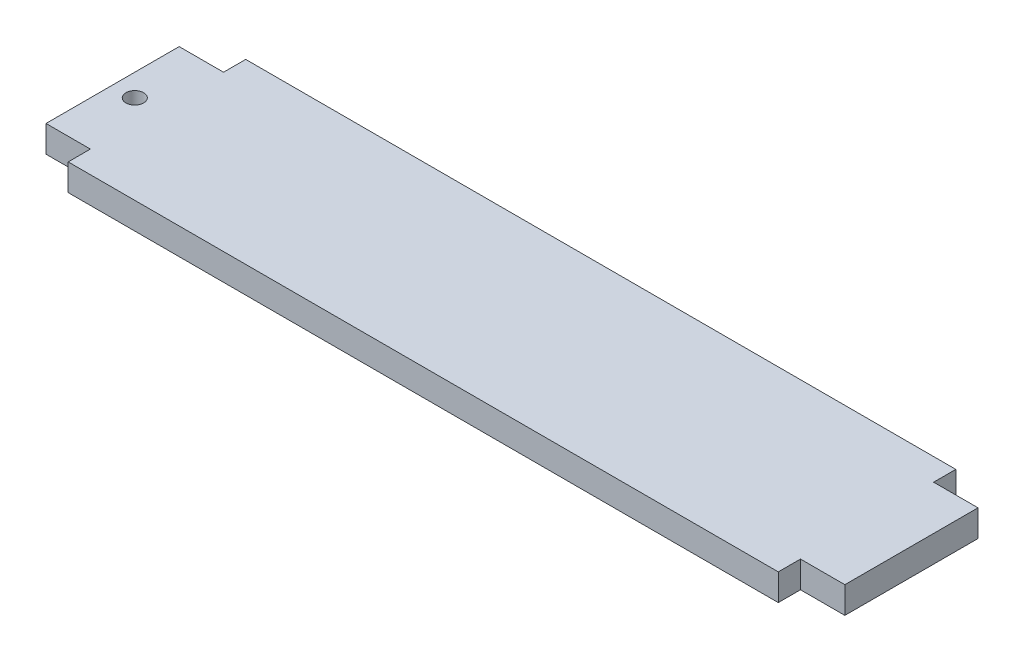
SolidWorks part; units mm, degrees
ref_plane "Front Plane" through (0, 0, 0) normal (0, 0, 1) x (1, 0, 0)
ref_plane "Top Plane" through (0, 0, 0) normal (0, 1, 0) x (1, 0, 0)
ref_plane "Right Plane" through (0, 0, 0) normal (1, 0, 0) x (0, 0, -1)
sketch "Sketch1" plane through (0, 0, 0) normal (1, 0, 0) x (0, 0, -1)
  line L1 (-10.1369, 5.602) -> (9.8631, 5.602)
  line L2 (-10.1369, 5.602) -> (-10.1369, 2.602)
  line L3 (-10.1369, 2.602) -> (9.8631, 2.602)
  line L4 (9.8631, 5.602) -> (9.8631, 2.602)
  dimension "D1" = 20
  dimension "D2" = 3
extrude "Boss-Extrude1" add sketch "Sketch1" along normal blind 90
sketch "Sketch2" plane through (0, 2.602, 0) normal (0, -1, 0) x (1, 0, 0)
  line L1 (0, -9.8631) -> (5, -9.8631)
  line L2 (0, -9.8631) -> (0, -7.3631)
  line L3 (0, -7.3631) -> (5, -7.3631)
  line L4 (5, -9.8631) -> (5, -7.3631)
  dimension "D1" = 5
  dimension "D2" = 2.5
extrude "Cut-Extrude1" cut sketch "Sketch2" against normal blind 90
sketch "Sketch5" plane through (0, 0, 0) normal (-1, 0, 0) x (0, 0, 1)
  line L0 (0, 2.602) -> (0, 5.602) construction
  line L1 (10.1369, 2.602) -> (-7.3631, 2.602) construction
  line L2 (-7.3631, 5.602) -> (10.1369, 5.602) construction
sketch "Sketch6" plane through (0, 5.602, 0) normal (0, 1, 0) x (1, 0, 0)
  line L1 (0, -10.1369) -> (5, -10.1369)
  line L2 (0, -10.1369) -> (0, -7.6369)
  line L3 (0, -7.6369) -> (5, -7.6369)
  line L4 (5, -10.1369) -> (5, -7.6369)
  dimension "D1" = 5
  dimension "D2" = 2.5
extrude "Cut-Extrude2" cut sketch "Sketch6" against normal blind 90 contours L3 L4 L1 L2
sketch "Sketch7" plane through (0, 5.602, 0) normal (0, 1, 0) x (1, 0, 0)
  line L0 (90, -0.1369) -> (0, 0) construction
  line L1 (90, 9.8631) -> (90, -10.1369) construction
  line L2 (45, -0.0684) -> (45, -10.1369) construction
  line L3 (90, -10.1369) -> (5, -10.1369) construction
sketch "Sketch8" plane through (0, 0, 10.1369) normal (0, 0, 1) x (1, 0, 0)
  line L0 (45, 5.602) -> (45, 2.602) construction
  line L1 (90, 2.602) -> (5, 2.602) construction
ref_plane "Plane3" through (45, 0, 0) normal (1, 0, 0) x (0, 0, -1)
mirror "Mirror2" about plane through (45, 0, 0) normal (1, 0, 0) of "Cut-Extrude1", "Cut-Extrude2"
sketch "Sketch9" plane through (0, 2.602, 0) normal (0, -1, 0) x (-1, 0, 0)
  line L0 (-2.5, 7.3631) -> (-2.5, -7.6369) construction
  line L1 (-5, 7.3631) -> (0, 7.3631) construction
  line L2 (0, -7.6369) -> (-5, -7.6369) construction
  line L3 (-2.5, -0.1369) -> (0, -0.1369) construction
  line L4 (0, -7.6369) -> (0, 7.3631) construction
hole_wizard "Ø2.0mm Dowel Hole1" positions "3DSketch1" profile "Sketch11" hole size "Ø2.0" standard "ISO"
sketch3d "3DSketch1"
  point P0 (2.5, 2.602, 0.1369)
sketch "Sketch11" plane through (2.5, 2.602, 0.1369) normal (1, 0, 0) x (0, 0, -1)
  line L0 (0, 0) -> (0, 13.3509)
  line L1 (0, 13.3509) -> (1, 12.75)
  line L2 (1, 12.75) -> (1, 0)
  line L5 (1, 0) -> (0, 0)
  line L10 (0, 13.3509) -> (-1, 12.75) construction
  line L11 (0, -6.35) -> (0, 107.95) construction
  dimension "Hole Dia." = 2
  dimension "Hole Depth" = 12.75
  dimension "Drill Angle" = 118
